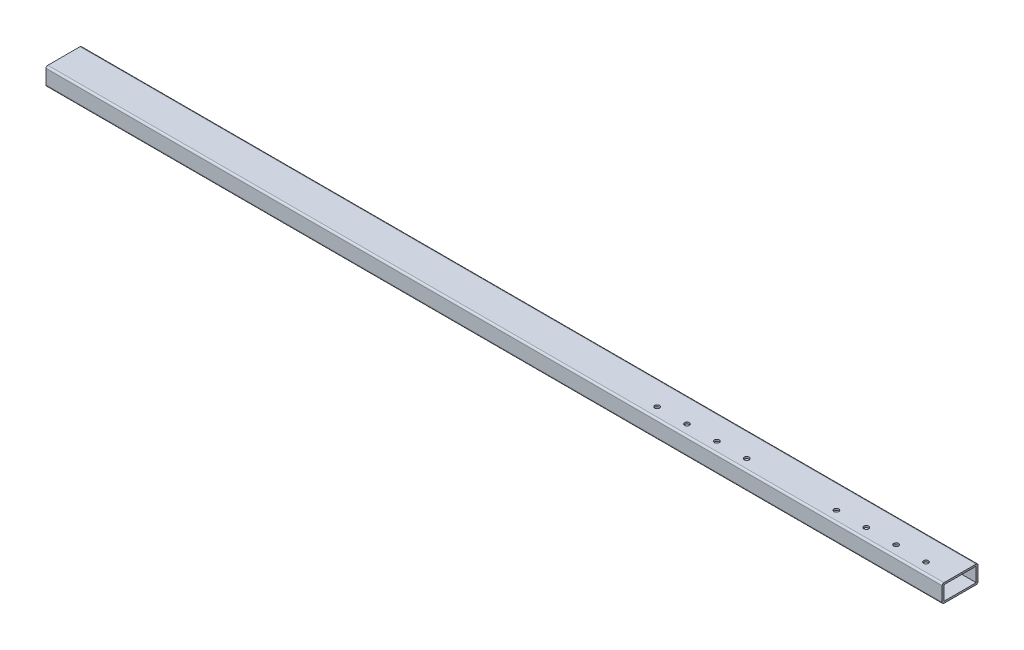
SolidWorks part; units mm, degrees
ref_plane "Спереди" through (0, 0, 0) normal (0, 0, 1) x (1, 0, 0)
ref_plane "Сверху" through (0, 0, 0) normal (0, 1, 0) x (1, 0, 0)
ref_plane "Справа" through (0, 0, 0) normal (1, 0, 0) x (0, 0, -1)
sketch "Эскиз1" plane through (0, 0, 0) normal (1, 0, 0) x (0, 0, -1)
  line L1 (-27, 15) -> (27, 15)
  line L2 (-30, 12) -> (-30, -12)
  line L3 (-27, -15) -> (27, -15)
  line L4 (30, 12) -> (30, -12)
  line L5 (-30, 15) -> (30, -15) construction
  line L6 (-30, -15) -> (30, 15) construction
  arc A0 (-27, 15) -> (-30, 12) centre (-27, 12) ccw
  arc A1 (-30, -12) -> (-27, -15) centre (-27, -12) ccw
  arc A2 (27, -15) -> (30, -12) centre (27, -12) ccw
  arc A3 (27, 15) -> (30, 12) centre (27, 12) cw
  point P0 (0, 0)
  dimension "D1" = 3
extrude "Вытянуть-Тонкостенный1" add sketch "Эскиз1" along normal blind 1500 thin thin type one direction reverse wall 3
sketch "Эскиз2" plane through (0, 15, 0) normal (0, 1, 0) x (1, 0, 0)
  circle A0 centre (1455, -12) radius 4.05
  circle A1 centre (1405, -12) radius 4.05
  circle A2 centre (1355, -12) radius 4.05
  circle A3 centre (1305, -12) radius 4.05
  circle A4 centre (1155, -12) radius 4.05
  circle A5 centre (1105, -12) radius 4.05
  circle A6 centre (1055, -12) radius 4.05
  circle A7 centre (1005, -12) radius 4.05
  dimension "D1" = 4
  dimension "D2" = 2
extrude "Вырез-Вытянуть1" cut sketch "Эскиз2" against normal through all
